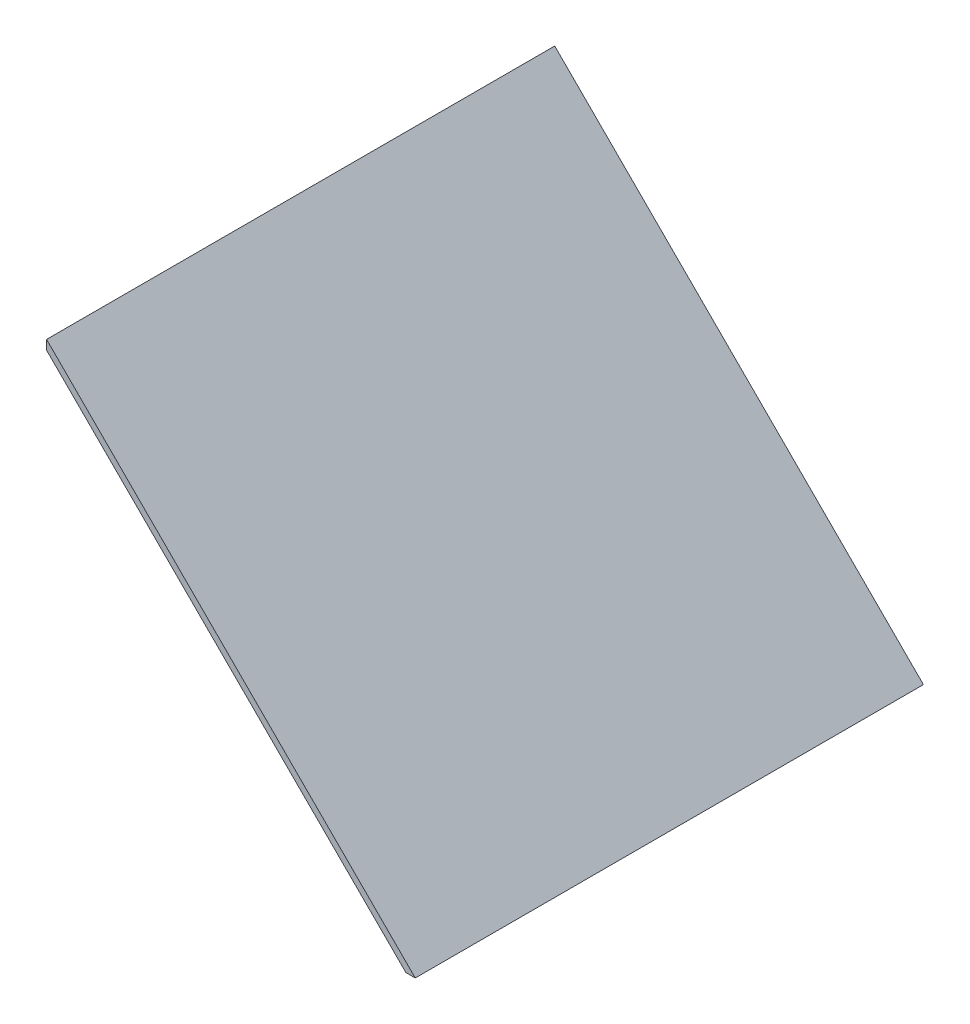
SolidWorks part; units mm, degrees
ref_plane "Front Plane" through (0, 0, 0) normal (0, 0, 1) x (1, 0, 0)
ref_plane "Top Plane" through (0, 0, 0) normal (0, 1, 0) x (1, 0, 0)
ref_plane "Right Plane" through (0, 0, 0) normal (1, 0, 0) x (0, 0, -1)
sketch "Sketch1" plane through (0, 0, 0) normal (0, 0, 1) x (1, 0, 0)
  line L0 (0, 0) -> (77.7817, -77.7817)
  line L9 (77.7817, -77.7817) -> (79.8137, -77.7817)
  line L10 (79.8137, -77.7817) -> (0, 2.032)
  line L12 (0, 2.032) -> (0, 0) construction
  point P0 (0, 0)
  dimension "D1" = 45
  dimension "D4" = 110
  dimension "D2" = 2.032
extrude "Boss-Extrude1" add sketch "Sketch1" along normal blind 110 contours L10 L12 L0 L9 region at (39.4011, -38.3807, 0)
sketch "Sketch2" plane through (1.016, 1.016, 0) normal (0.7071, 0.7071, 0) x (0, 0, -1)
  line L1 (-105, -6.4368) -> (-5, -6.4368) construction
  line L2 (-105, -6.4368) -> (-105, -106.4368) construction
  line L3 (-105, -106.4368) -> (-5, -106.4368) construction
  line L4 (-5, -6.4368) -> (-5, -106.4368) construction
  line L8 (-110, -111.4368) -> (0, -111.4368) construction
  line L9 (0, -111.4368) -> (0, 1.4368) construction
  circle A0 centre (-55, -56.4368) radius 50.8 construction
  point P8 (-55, -97.7238)
  point P10 (-55, -6.4368)
  point P12 (0, 0)
  point P13 (-5, -56.4368)
  dimension "D4" = 101.6
  dimension "D1" = 100
  dimension "D3" = 5
  dimension "D2" = 5
ref_axis "Axis1" through (87.3651, -38.8909, 55) along (-1, 0, 0)
equation "\"width\"=110"
equation "\"D1@Boss-Extrude1\"=\"width\""
equation "\"height\"= 110"
equation "\"D4@Sketch1\"=\"height\""
equation "\"D3@Sketch2\"=(\"height\" - \"D1@Sketch2\")/2"
equation "\"D2@Sketch2\"=(\"width\"-\"D1@Sketch2\")/2"
